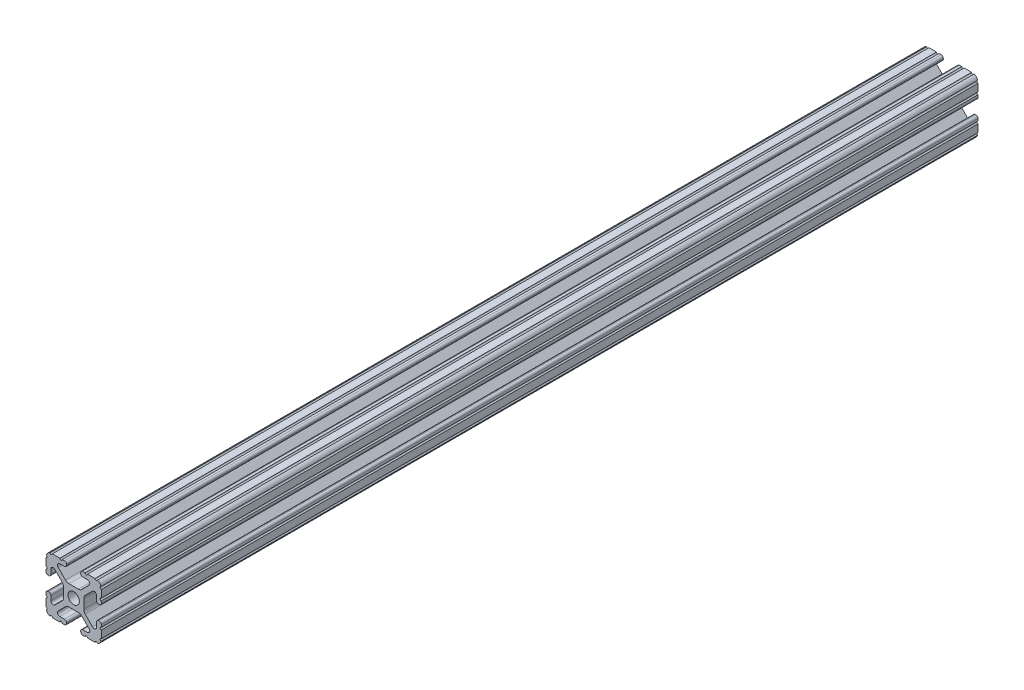
SolidWorks part; units mm, degrees
ref_plane "Front Plane" through (0, 0, 0) normal (0, 0, 1) x (1, 0, 0)
ref_plane "Top Plane" through (0, 0, 0) normal (0, 1, 0) x (1, 0, 0)
ref_plane "Right Plane" through (0, 0, 0) normal (1, 0, 0) x (0, 0, -1)
other "Configuration Table"
sketch "Sketch2" plane through (0, 0, 0) normal (0, 0, 1) x (1, 0, 0)
  line L0 (0, 12.7) -> (0, -12.7) construction
  line L1 (-12.7, 0) -> (12.7, 0) construction
  line L2 (3.2512, -12.7) -> (12.7, -12.7)
  line L3 (12.7, -12.7) -> (12.7, -3.2512)
  line L4 (3.2512, -12.7) -> (3.2512, -10.4902)
  line L5 (3.2512, -10.4902) -> (8.9276, -10.4902)
  line L6 (8.9276, -10.4902) -> (3.0856, -4.6482)
  line L7 (0, 0) -> (12.7, -12.7) construction
  line L8 (12.7, -3.2512) -> (10.4902, -3.2512)
  line L9 (10.4902, -3.2512) -> (10.4902, -8.9276)
  line L10 (10.4902, -8.9276) -> (4.6482, -3.0856)
  circle A0 centre (0, 0) radius 2.6035
  arc A1 (6.3485, -10.4902) -> (7.1039, -8.6665) centre (6.3485, -9.4219) ccw construction
  point P8 (0, -4.6482)
  dimension "Center Hole Diameter" = 5.207
  dimension "Rail Height" = 25.4
  dimension "Rail Width" = 25.4
  dimension "T-Slot Width" = 6.5024
  dimension "Slot Inner Width" = 14.8336
  dimension "Thickness" = 2.2098
  dimension "Slot Depth" = 5.842
  dimension "D1" = 2.2098
sketch "Sketch3" plane through (0, 0, 0) normal (1, 0, 0) x (0, 0, -1)
  line L0 (-113.37, -12.7) -> (113.37, -12.7) construction
  line L1 (-102.033, 0) -> (102.033, 0) construction
  dimension "Length" = 226.74
  dimension "D1" = 204.066
sketch "Sketch4" plane through (0, 0, 0) normal (0, 0, 1) x (1, 0, 0)
  line L0 (4.1904, -12.7) -> (10.1173, -12.7)
  line L1 (3.2512, -12.7) -> (12.7, -12.7) construction
  line L2 (3.2512, -12.7) -> (3.2512, -10.4902) construction
  line L3 (3.2512, -10.4902) -> (8.9276, -10.4902) construction
  line L4 (3.2512, -11.4294) -> (3.2512, -11.7608)
  line L5 (4.1904, -10.4902) -> (6.3485, -10.4902)
  line L6 (0, -4.6482) -> (2.164, -4.6482)
  line L7 (8.9276, -10.4902) -> (3.0856, -4.6482) construction
  line L8 (3.7373, -5.2999) -> (7.1039, -8.6665)
  line L9 (12.7, -12.7) -> (12.7, -3.2512) construction
  line L10 (10.4902, -8.9276) -> (4.6482, -3.0856) construction
  line L11 (10.4902, -3.2512) -> (10.4902, -8.9276) construction
  line L12 (10.4902, -6.3485) -> (10.4902, -4.1904)
  line L13 (12.7, -3.2512) -> (10.4902, -3.2512) construction
  line L14 (11.4294, -3.2512) -> (11.7608, -3.2512)
  line L15 (12.7, -4.1904) -> (12.7, -10.1173)
  line L16 (8.6665, -7.1039) -> (5.2999, -3.7373)
  line L17 (4.6482, 0) -> (4.6482, -2.164)
  line L18 (-12.7, 0) -> (12.7, 0) construction
  line L19 (0, -4.6482) -> (0, -2.6035)
  line L20 (0, 12.7) -> (0, -12.7) construction
  line L21 (4.6482, 0) -> (2.6035, 0)
  arc A0 (3.2512, -11.7608) -> (4.1904, -12.7) centre (4.1904, -11.7608) ccw
  arc A2 (3.2512, -11.4294) -> (4.1904, -10.4902) centre (4.1904, -11.4294) cw
  arc A3 (6.3485, -10.4902) -> (7.1039, -8.6665) centre (6.3485, -9.4219) ccw
  arc A4 (2.164, -4.6482) -> (3.7373, -5.2999) centre (2.164, -6.8732) cw
  arc A5 (10.1173, -12.7) -> (12.7, -10.1173) centre (10.1173, -10.1173) ccw
  arc A6 (8.6665, -7.1039) -> (10.4902, -6.3485) centre (9.4219, -6.3485) ccw
  arc A7 (10.4902, -4.1904) -> (11.4294, -3.2512) centre (11.4294, -4.1904) cw
  arc A8 (11.7608, -3.2512) -> (12.7, -4.1904) centre (11.7608, -4.1904) cw
  arc A9 (5.2999, -3.7373) -> (4.6482, -2.164) centre (6.8732, -2.164) cw
  circle A10 centre (0, 0) radius 2.6035 construction
  arc A11 (0, -2.6035) -> (2.6035, 0) centre (0, 0) ccw
  dimension "D1" = 2.5827
  dimension "D2" = 2.225
  dimension "D3" = 0.9392
extrude "Boss-Extrude1" add sketch "Sketch4" along normal mid plane 226.74
sketch "Sketch5" plane through (0, 0, 0) normal (0, 0, 1) x (1, 0, 0)
  line L0 (3.2512, -12.7) -> (12.7, -12.7) construction
  line L1 (4.1904, -10.4902) -> (6.3485, -10.4902) construction
  line L3 (0, 0) -> (12.7, -12.7) construction
  line L4 (6.3485, -10.4902) -> (6.3485, -12.7) construction
  line L5 (8.9276, -10.4902) -> (3.0856, -4.6482) construction
  circle A0 centre (10.3562, -12.7) radius 0.5524
  circle A1 centre (5.796, -12.7) radius 0.5524
  circle A2 centre (12.7, -10.3562) radius 0.5524
  circle A3 centre (12.7, -5.796) radius 0.5524
  point P10 (5.2694, -10.4902)
  point P12 (9.4219, -6.3485)
  dimension "D1" = 1.1049
extrude "Cut-Extrude1" cut sketch "Sketch5" against normal through all both and the other way through all
mirror "Mirror1" about plane through (0, 0, 0) normal (1, 0, 0) of bodies 137 134
mirror "Mirror2" about plane through (0, 0, 0) normal (0, 1, 0) of bodies 135
sketch "Sketch6" plane through (0, 0, 113.37) normal (0, 0, 1) x (1, 0, 0)
  line L44 (12.7, -5.2436) -> (12.7, -4.1904)
  line L45 (11.7608, -3.2512) -> (11.4294, -3.2512)
  line L46 (10.4902, -4.1904) -> (10.4902, -6.3485)
  line L47 (8.6665, -7.1039) -> (5.2999, -3.7373)
  line L48 (4.6482, -2.164) -> (4.6482, 2.164)
  line L49 (5.2999, 3.7373) -> (8.6665, 7.1039)
  line L50 (10.4902, 6.3485) -> (10.4902, 4.1904)
  line L51 (11.4294, 3.2512) -> (11.7608, 3.2512)
  line L52 (12.7, 4.1904) -> (12.7, 5.2436)
  line L53 (12.7, 6.3485) -> (12.7, 9.8037)
  line L54 (9.8037, 12.7) -> (6.3485, 12.7)
  line L55 (5.2436, 12.7) -> (4.1904, 12.7)
  line L56 (3.2512, 11.7608) -> (3.2512, 11.4294)
  line L57 (4.1904, 10.4902) -> (6.3485, 10.4902)
  line L58 (7.1039, 8.6665) -> (3.7373, 5.2999)
  line L59 (2.164, 4.6482) -> (-2.164, 4.6482)
  line L60 (-3.7373, 5.2999) -> (-7.1039, 8.6665)
  line L61 (-6.3485, 10.4902) -> (-4.1904, 10.4902)
  line L62 (-3.2512, 11.4294) -> (-3.2512, 11.7608)
  line L63 (-4.1904, 12.7) -> (-5.2436, 12.7)
  line L64 (-6.3485, 12.7) -> (-9.8037, 12.7)
  line L65 (-12.7, 9.8037) -> (-12.7, 6.3485)
  line L66 (-12.7, 5.2436) -> (-12.7, 4.1904)
  line L67 (-11.7608, 3.2512) -> (-11.4294, 3.2512)
  line L68 (-10.4902, 4.1904) -> (-10.4902, 6.3485)
  line L69 (-8.6665, 7.1039) -> (-5.2999, 3.7373)
  line L70 (-4.6482, 2.164) -> (-4.6482, -2.164)
  line L71 (-5.2999, -3.7373) -> (-8.6665, -7.1039)
  line L72 (-10.4902, -6.3485) -> (-10.4902, -4.1904)
  line L73 (-11.4294, -3.2512) -> (-11.7608, -3.2512)
  line L74 (-12.7, -4.1904) -> (-12.7, -5.2436)
  line L75 (-12.7, -6.3485) -> (-12.7, -9.8037)
  line L76 (-9.8037, -12.7) -> (-6.3485, -12.7)
  line L77 (-5.2436, -12.7) -> (-4.1904, -12.7)
  line L78 (-3.2512, -11.7608) -> (-3.2512, -11.4294)
  line L79 (-4.1904, -10.4902) -> (-6.3485, -10.4902)
  line L80 (-7.1039, -8.6665) -> (-3.7373, -5.2999)
  line L81 (-2.164, -4.6482) -> (2.164, -4.6482)
  line L82 (3.7373, -5.2999) -> (7.1039, -8.6665)
  line L83 (6.3485, -10.4902) -> (4.1904, -10.4902)
  line L84 (3.2512, -11.4294) -> (3.2512, -11.7608)
  line L85 (4.1904, -12.7) -> (5.2436, -12.7)
  line L86 (6.3485, -12.7) -> (9.8037, -12.7)
  line L87 (12.7, -9.8037) -> (12.7, -6.3485)
  line L88 (12.7, -5.2436) -> (12.7, -4.1904)
  line L89 (11.7608, -3.2512) -> (11.4294, -3.2512)
  line L90 (10.4902, -4.1904) -> (10.4902, -6.3485)
  line L91 (8.6665, -7.1039) -> (5.2999, -3.7373)
  line L92 (4.6482, -2.164) -> (4.6482, 2.164)
  line L93 (5.2999, 3.7373) -> (8.6665, 7.1039)
  line L94 (10.4902, 6.3485) -> (10.4902, 4.1904)
  line L95 (11.4294, 3.2512) -> (11.7608, 3.2512)
  line L96 (12.7, 4.1904) -> (12.7, 5.2436)
  line L97 (12.7, 6.3485) -> (12.7, 9.8037)
  line L98 (9.8037, 12.7) -> (6.3485, 12.7)
  line L99 (5.2436, 12.7) -> (4.1904, 12.7)
  line L100 (3.2512, 11.7608) -> (3.2512, 11.4294)
  line L101 (4.1904, 10.4902) -> (6.3485, 10.4902)
  line L102 (7.1039, 8.6665) -> (3.7373, 5.2999)
  line L103 (2.164, 4.6482) -> (-2.164, 4.6482)
  line L104 (-3.7373, 5.2999) -> (-7.1039, 8.6665)
  line L105 (-6.3485, 10.4902) -> (-4.1904, 10.4902)
  line L106 (-3.2512, 11.4294) -> (-3.2512, 11.7608)
  line L107 (-4.1904, 12.7) -> (-5.2436, 12.7)
  line L108 (-6.3485, 12.7) -> (-9.8037, 12.7)
  line L109 (-12.7, 9.8037) -> (-12.7, 6.3485)
  line L110 (-12.7, 5.2436) -> (-12.7, 4.1904)
  line L111 (-11.7608, 3.2512) -> (-11.4294, 3.2512)
  line L112 (-10.4902, 4.1904) -> (-10.4902, 6.3485)
  line L113 (-8.6665, 7.1039) -> (-5.2999, 3.7373)
  line L114 (-4.6482, 2.164) -> (-4.6482, -2.164)
  line L115 (-5.2999, -3.7373) -> (-8.6665, -7.1039)
  line L116 (-10.4902, -6.3485) -> (-10.4902, -4.1904)
  line L117 (-11.4294, -3.2512) -> (-11.7608, -3.2512)
  line L118 (-12.7, -4.1904) -> (-12.7, -5.2436)
  line L119 (-12.7, -6.3485) -> (-12.7, -9.8037)
  line L120 (-9.8037, -12.7) -> (-6.3485, -12.7)
  line L121 (-5.2436, -12.7) -> (-4.1904, -12.7)
  line L122 (-3.2512, -11.7608) -> (-3.2512, -11.4294)
  line L123 (-4.1904, -10.4902) -> (-6.3485, -10.4902)
  line L124 (-7.1039, -8.6665) -> (-3.7373, -5.2999)
  line L125 (-2.164, -4.6482) -> (2.164, -4.6482)
  line L126 (3.7373, -5.2999) -> (7.1039, -8.6665)
  line L127 (6.3485, -10.4902) -> (4.1904, -10.4902)
  line L128 (3.2512, -11.4294) -> (3.2512, -11.7608)
  line L129 (4.1904, -12.7) -> (5.2436, -12.7)
  line L130 (6.3485, -12.7) -> (9.8037, -12.7)
  line L131 (12.7, -9.8037) -> (12.7, -6.3485)
  circle A0 centre (0, 0) radius 2.6035
  arc A52 (12.7, -5.2436) -> (12.7, -6.3485) centre (12.7, -5.796) ccw
  arc A53 (12.7, -4.1904) -> (11.7608, -3.2512) centre (11.7608, -4.1904) ccw
  arc A54 (11.4294, -3.2512) -> (10.4902, -4.1904) centre (11.4294, -4.1904) ccw
  arc A55 (8.6665, -7.1039) -> (10.4902, -6.3485) centre (9.4219, -6.3485) ccw
  arc A56 (4.6482, -2.164) -> (5.2999, -3.7373) centre (6.8732, -2.164) ccw
  arc A57 (5.2999, 3.7373) -> (4.6482, 2.164) centre (6.8732, 2.164) ccw
  arc A58 (10.4902, 6.3485) -> (8.6665, 7.1039) centre (9.4219, 6.3485) ccw
  arc A59 (10.4902, 4.1904) -> (11.4294, 3.2512) centre (11.4294, 4.1904) ccw
  arc A60 (11.7608, 3.2512) -> (12.7, 4.1904) centre (11.7608, 4.1904) ccw
  arc A61 (12.7, 6.3485) -> (12.7, 5.2436) centre (12.7, 5.796) ccw
  arc A62 (12.58, 10.8954) -> (12.7, 9.8037) centre (12.7, 10.3562) ccw
  arc A63 (12.58, 10.8954) -> (10.8954, 12.58) centre (10.1173, 10.1173) ccw
  arc A64 (9.8037, 12.7) -> (10.8954, 12.58) centre (10.3562, 12.7) ccw
  arc A65 (5.2436, 12.7) -> (6.3485, 12.7) centre (5.796, 12.7) ccw
  arc A66 (4.1904, 12.7) -> (3.2512, 11.7608) centre (4.1904, 11.7608) ccw
  arc A67 (3.2512, 11.4294) -> (4.1904, 10.4902) centre (4.1904, 11.4294) ccw
  arc A68 (7.1039, 8.6665) -> (6.3485, 10.4902) centre (6.3485, 9.4219) ccw
  arc A69 (2.164, 4.6482) -> (3.7373, 5.2999) centre (2.164, 6.8732) ccw
  arc A70 (-3.7373, 5.2999) -> (-2.164, 4.6482) centre (-2.164, 6.8732) ccw
  arc A71 (-6.3485, 10.4902) -> (-7.1039, 8.6665) centre (-6.3485, 9.4219) ccw
  arc A72 (-4.1904, 10.4902) -> (-3.2512, 11.4294) centre (-4.1904, 11.4294) ccw
  arc A73 (-3.2512, 11.7608) -> (-4.1904, 12.7) centre (-4.1904, 11.7608) ccw
  arc A74 (-6.3485, 12.7) -> (-5.2436, 12.7) centre (-5.796, 12.7) ccw
  arc A75 (-10.8954, 12.58) -> (-9.8037, 12.7) centre (-10.3562, 12.7) ccw
  arc A76 (-10.8954, 12.58) -> (-12.58, 10.8954) centre (-10.1173, 10.1173) ccw
  arc A77 (-12.7, 9.8037) -> (-12.58, 10.8954) centre (-12.7, 10.3562) ccw
  arc A78 (-12.7, 5.2436) -> (-12.7, 6.3485) centre (-12.7, 5.796) ccw
  arc A79 (-12.7, 4.1904) -> (-11.7608, 3.2512) centre (-11.7608, 4.1904) ccw
  arc A80 (-11.4294, 3.2512) -> (-10.4902, 4.1904) centre (-11.4294, 4.1904) ccw
  arc A81 (-8.6665, 7.1039) -> (-10.4902, 6.3485) centre (-9.4219, 6.3485) ccw
  arc A82 (-4.6482, 2.164) -> (-5.2999, 3.7373) centre (-6.8732, 2.164) ccw
  arc A83 (-5.2999, -3.7373) -> (-4.6482, -2.164) centre (-6.8732, -2.164) ccw
  arc A84 (-10.4902, -6.3485) -> (-8.6665, -7.1039) centre (-9.4219, -6.3485) ccw
  arc A85 (-10.4902, -4.1904) -> (-11.4294, -3.2512) centre (-11.4294, -4.1904) ccw
  arc A86 (-11.7608, -3.2512) -> (-12.7, -4.1904) centre (-11.7608, -4.1904) ccw
  arc A87 (-12.7, -6.3485) -> (-12.7, -5.2436) centre (-12.7, -5.796) ccw
  arc A88 (-12.58, -10.8954) -> (-12.7, -9.8037) centre (-12.7, -10.3562) ccw
  arc A89 (-12.58, -10.8954) -> (-10.8954, -12.58) centre (-10.1173, -10.1173) ccw
  arc A90 (-9.8037, -12.7) -> (-10.8954, -12.58) centre (-10.3562, -12.7) ccw
  arc A91 (-5.2436, -12.7) -> (-6.3485, -12.7) centre (-5.796, -12.7) ccw
  arc A92 (-4.1904, -12.7) -> (-3.2512, -11.7608) centre (-4.1904, -11.7608) ccw
  arc A93 (-3.2512, -11.4294) -> (-4.1904, -10.4902) centre (-4.1904, -11.4294) ccw
  arc A94 (-7.1039, -8.6665) -> (-6.3485, -10.4902) centre (-6.3485, -9.4219) ccw
  arc A95 (-2.164, -4.6482) -> (-3.7373, -5.2999) centre (-2.164, -6.8732) ccw
  arc A96 (3.7373, -5.2999) -> (2.164, -4.6482) centre (2.164, -6.8732) ccw
  arc A97 (6.3485, -10.4902) -> (7.1039, -8.6665) centre (6.3485, -9.4219) ccw
  arc A98 (4.1904, -10.4902) -> (3.2512, -11.4294) centre (4.1904, -11.4294) ccw
  arc A99 (3.2512, -11.7608) -> (4.1904, -12.7) centre (4.1904, -11.7608) ccw
  arc A100 (6.3485, -12.7) -> (5.2436, -12.7) centre (5.796, -12.7) ccw
  arc A101 (10.8954, -12.58) -> (9.8037, -12.7) centre (10.3562, -12.7) ccw
  arc A102 (10.8954, -12.58) -> (12.58, -10.8954) centre (10.1173, -10.1173) ccw
  arc A103 (12.7, -9.8037) -> (12.58, -10.8954) centre (12.7, -10.3562) ccw
  arc A104 (12.7, -5.2436) -> (12.7, -6.3485) centre (12.7, -5.796) ccw
  arc A105 (12.7, -4.1904) -> (11.7608, -3.2512) centre (11.7608, -4.1904) ccw
  arc A106 (11.4294, -3.2512) -> (10.4902, -4.1904) centre (11.4294, -4.1904) ccw
  arc A107 (8.6665, -7.1039) -> (10.4902, -6.3485) centre (9.4219, -6.3485) ccw
  arc A108 (4.6482, -2.164) -> (5.2999, -3.7373) centre (6.8732, -2.164) ccw
  arc A109 (5.2999, 3.7373) -> (4.6482, 2.164) centre (6.8732, 2.164) ccw
  arc A110 (10.4902, 6.3485) -> (8.6665, 7.1039) centre (9.4219, 6.3485) ccw
  arc A111 (10.4902, 4.1904) -> (11.4294, 3.2512) centre (11.4294, 4.1904) ccw
  arc A112 (11.7608, 3.2512) -> (12.7, 4.1904) centre (11.7608, 4.1904) ccw
  arc A113 (12.7, 6.3485) -> (12.7, 5.2436) centre (12.7, 5.796) ccw
  arc A114 (12.58, 10.8954) -> (12.7, 9.8037) centre (12.7, 10.3562) ccw
  arc A115 (12.58, 10.8954) -> (10.8954, 12.58) centre (10.1173, 10.1173) ccw
  arc A116 (9.8037, 12.7) -> (10.8954, 12.58) centre (10.3562, 12.7) ccw
  arc A117 (5.2436, 12.7) -> (6.3485, 12.7) centre (5.796, 12.7) ccw
  arc A118 (4.1904, 12.7) -> (3.2512, 11.7608) centre (4.1904, 11.7608) ccw
  arc A119 (3.2512, 11.4294) -> (4.1904, 10.4902) centre (4.1904, 11.4294) ccw
  arc A120 (7.1039, 8.6665) -> (6.3485, 10.4902) centre (6.3485, 9.4219) ccw
  arc A121 (2.164, 4.6482) -> (3.7373, 5.2999) centre (2.164, 6.8732) ccw
  arc A122 (-3.7373, 5.2999) -> (-2.164, 4.6482) centre (-2.164, 6.8732) ccw
  arc A123 (-6.3485, 10.4902) -> (-7.1039, 8.6665) centre (-6.3485, 9.4219) ccw
  arc A124 (-4.1904, 10.4902) -> (-3.2512, 11.4294) centre (-4.1904, 11.4294) ccw
  arc A125 (-3.2512, 11.7608) -> (-4.1904, 12.7) centre (-4.1904, 11.7608) ccw
  arc A126 (-6.3485, 12.7) -> (-5.2436, 12.7) centre (-5.796, 12.7) ccw
  arc A127 (-10.8954, 12.58) -> (-9.8037, 12.7) centre (-10.3562, 12.7) ccw
  arc A128 (-10.8954, 12.58) -> (-12.58, 10.8954) centre (-10.1173, 10.1173) ccw
  arc A129 (-12.7, 9.8037) -> (-12.58, 10.8954) centre (-12.7, 10.3562) ccw
  arc A130 (-12.7, 5.2436) -> (-12.7, 6.3485) centre (-12.7, 5.796) ccw
  arc A131 (-12.7, 4.1904) -> (-11.7608, 3.2512) centre (-11.7608, 4.1904) ccw
  arc A132 (-11.4294, 3.2512) -> (-10.4902, 4.1904) centre (-11.4294, 4.1904) ccw
  arc A133 (-8.6665, 7.1039) -> (-10.4902, 6.3485) centre (-9.4219, 6.3485) ccw
  arc A134 (-4.6482, 2.164) -> (-5.2999, 3.7373) centre (-6.8732, 2.164) ccw
  arc A135 (-5.2999, -3.7373) -> (-4.6482, -2.164) centre (-6.8732, -2.164) ccw
  arc A136 (-10.4902, -6.3485) -> (-8.6665, -7.1039) centre (-9.4219, -6.3485) ccw
  arc A137 (-10.4902, -4.1904) -> (-11.4294, -3.2512) centre (-11.4294, -4.1904) ccw
  arc A138 (-11.7608, -3.2512) -> (-12.7, -4.1904) centre (-11.7608, -4.1904) ccw
  arc A139 (-12.7, -6.3485) -> (-12.7, -5.2436) centre (-12.7, -5.796) ccw
  arc A140 (-12.58, -10.8954) -> (-12.7, -9.8037) centre (-12.7, -10.3562) ccw
  arc A141 (-12.58, -10.8954) -> (-10.8954, -12.58) centre (-10.1173, -10.1173) ccw
  arc A142 (-9.8037, -12.7) -> (-10.8954, -12.58) centre (-10.3562, -12.7) ccw
  arc A143 (-5.2436, -12.7) -> (-6.3485, -12.7) centre (-5.796, -12.7) ccw
  arc A144 (-4.1904, -12.7) -> (-3.2512, -11.7608) centre (-4.1904, -11.7608) ccw
  arc A145 (-3.2512, -11.4294) -> (-4.1904, -10.4902) centre (-4.1904, -11.4294) ccw
  arc A146 (-7.1039, -8.6665) -> (-6.3485, -10.4902) centre (-6.3485, -9.4219) ccw
  arc A147 (-2.164, -4.6482) -> (-3.7373, -5.2999) centre (-2.164, -6.8732) ccw
  arc A148 (3.7373, -5.2999) -> (2.164, -4.6482) centre (2.164, -6.8732) ccw
  arc A149 (6.3485, -10.4902) -> (7.1039, -8.6665) centre (6.3485, -9.4219) ccw
  arc A150 (4.1904, -10.4902) -> (3.2512, -11.4294) centre (4.1904, -11.4294) ccw
  arc A151 (3.2512, -11.7608) -> (4.1904, -12.7) centre (4.1904, -11.7608) ccw
  arc A152 (6.3485, -12.7) -> (5.2436, -12.7) centre (5.796, -12.7) ccw
  arc A153 (10.8954, -12.58) -> (9.8037, -12.7) centre (10.3562, -12.7) ccw
  arc A154 (10.8954, -12.58) -> (12.58, -10.8954) centre (10.1173, -10.1173) ccw
  arc A155 (12.7, -9.8037) -> (12.58, -10.8954) centre (12.7, -10.3562) ccw
  dimension "D1" = 0
extrude "Boss-Extrude2" add sketch "Sketch6" along normal blind 175.92
equation "\"D1@Boss-Extrude1\"=\"Length@Sketch3\""
equation "\"D1@Sketch2\"=\"Thickness@Sketch2\""
equation "\"D2@Sketch4\"=\"Slot Inner Width@Sketch2\"*0.15"
equation "\"D1@Sketch4\"=\"D3@Sketch4\"*2.75"
equation "\"D3@Sketch4\"=\"Thickness@Sketch2\"*0.425"
equation "\"D1@Sketch5\"=\"Thickness@Sketch2\"*0.5"
equation "\"D1@Sketch3\"=\"Length@Sketch3\"*0.9"
